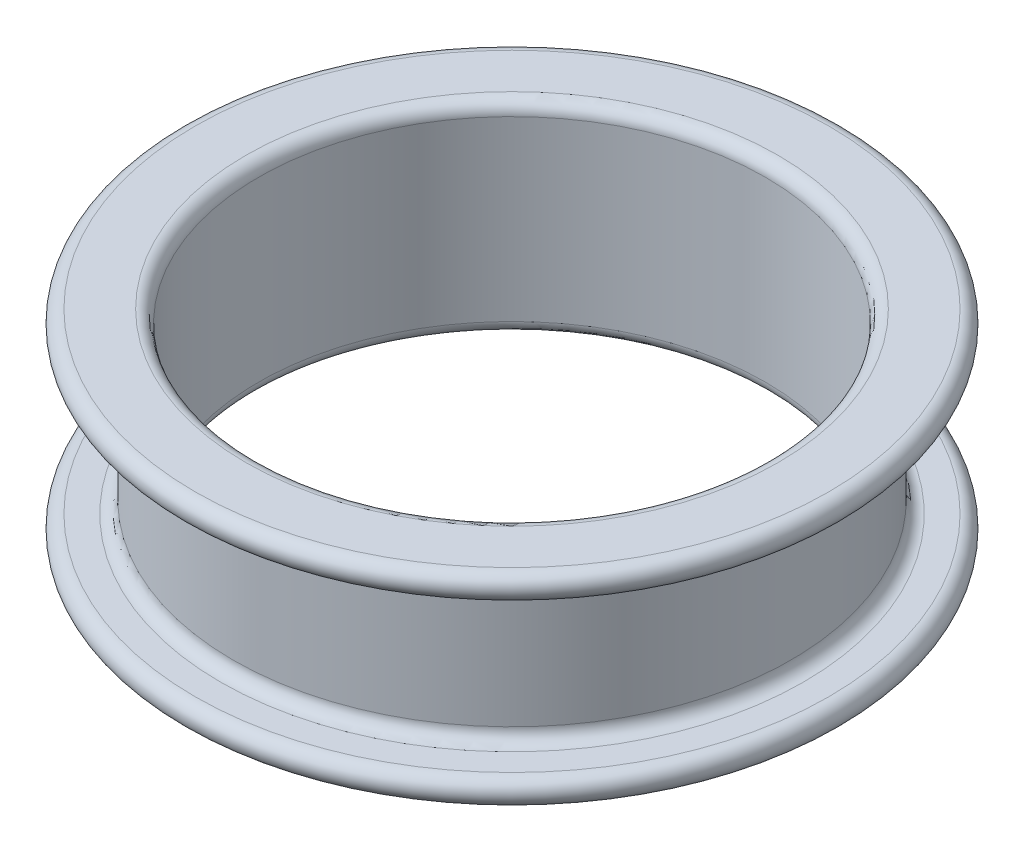
SolidWorks part; units mm, degrees
material "Chrome Stainless Steel"
ref_plane "Front Plane" through (0, 0, 0) normal (1, 0, 0) x (0, 1, 0)
ref_plane "Top Plane" through (0, 0, 0) normal (0, 0, 1) x (0, 1, 0)
ref_plane "Right Plane" through (0, 0, 0) normal (0, 1, 0) x (-1, 0, 0)
sketch "Sketch2" plane through (0, 0, 0) normal (1, 0, 0) x (0, 1, 0)
  line L0 (0, 20.6942) -> (0, -18.6446) construction
  line L1 (-17.2757, 0) -> (16.3772, 0) construction
  line L2 (-4, 10) -> (-4, 13)
  line L3 (-4, 13) -> (-3, 13)
  line L4 (-3, 13) -> (-3, 11)
  line L5 (-3, 11) -> (3, 11)
  line L6 (3, 11) -> (3, 13)
  line L7 (3, 13) -> (4, 13)
  line L8 (4, 13) -> (4, 10)
  line L9 (4, 10) -> (-4, 10)
  point P14 (0, 10)
  point P15 (0, 11)
  dimension "D1" = 11
  dimension "D2" = 8
  dimension "D3" = 6
  dimension "D4" = 20
  dimension "D5" = 26
revolve "Revolve1" add sketch "Sketch2" angle 360 about L1
fillet "Fillet1" radius 0.5 4 edges at (0, -3, -11) (0, 4, -10) (0, 3, -11) (0, -4, -10)
fillet "Fillet2" 2 edges at (0, 4, -13) (0, 3, -13) type full round first side face at (0, 4, -10.5) second side face at (0, 3, 11.5) middle face at (0, 3, -13)
fillet "Fillet3" 2 edges at (0, -3, -13) (0, -4, -13) type full round first side face at (0, -3, -11.5) second side face at (0, -4, 10.5) middle face at (0, -4, -13)
ref_axis "Axis1" through (0, 4.4, 0) along (0, -1, 0)
